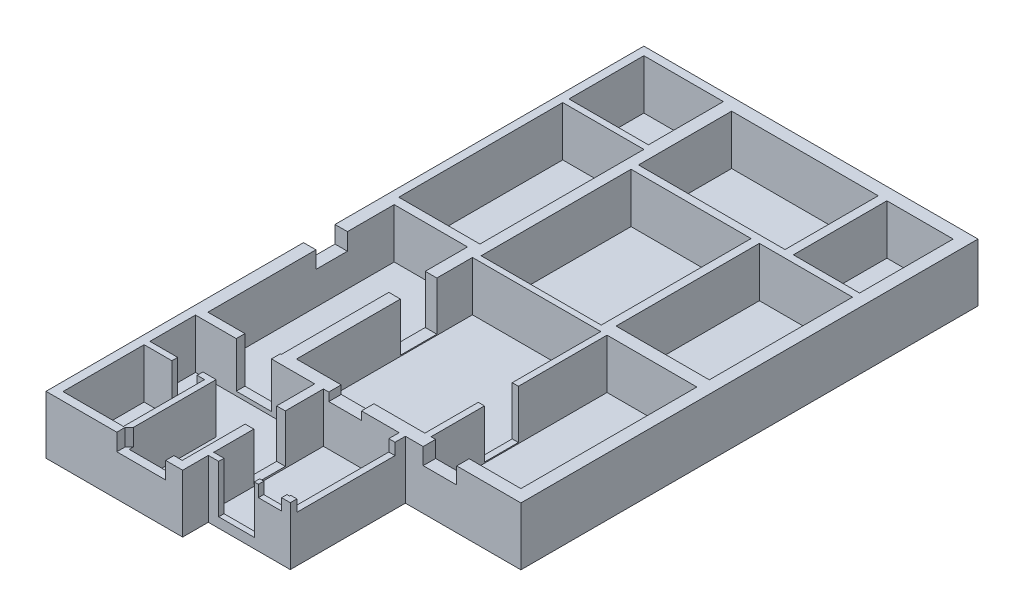
SolidWorks part; units mm, degrees
ref_plane "Спереди" through (0, 0, 0) normal (0, 0, 1) x (1, 0, 0)
ref_plane "Сверху" through (0, 0, 0) normal (0, 1, 0) x (1, 0, 0)
ref_plane "Справа" through (0, 0, 0) normal (1, 0, 0) x (0, 0, -1)
sketch "Эскиз1" plane through (0, 0, 0) normal (0, 1, 0) x (1, 0, 0)
  line L0 (-3589.779, 4492.6381) -> (-3589.779, 2682.6381)
  line L1 (-3789.779, -9747.3619) -> (-489.779, -9747.3619)
  line L2 (-3789.779, -9747.3619) -> (-3789.779, 4692.6381)
  line L3 (-3789.779, 4692.6381) -> (4280.221, 4692.6381)
  line L4 (4280.221, -6347.3619) -> (4280.221, 4692.6381)
  line L5 (-3789.779, -9747.3619) -> (4280.221, 4692.6381) construction
  line L6 (-3789.779, 4692.6381) -> (4280.221, -9747.3619) construction
  line L7 (-3589.779, 4492.6381) -> (-1669.779, 4492.6381)
  line L8 (-1629.779, 2532.6381) -> (-3589.779, 2532.6381)
  line L9 (3980.221, 4392.6381) -> (2380.221, 4392.6381)
  line L10 (-489.779, -9747.3619) -> (-489.779, -9127.3619)
  line L11 (-489.779, -9127.3619) -> (1490.221, -9127.3619)
  line L12 (1490.221, -9127.3619) -> (1490.221, -6347.3619)
  line L13 (1490.221, -6347.3619) -> (4280.221, -6347.3619)
  line L14 (4280.221, -6347.3619) -> (4280.221, -9747.3619) construction
  line L15 (-489.779, -9747.3619) -> (4280.221, -9747.3619) construction
  line L16 (3980.221, -6047.3619) -> (3980.221, -1797.3619)
  line L17 (1810.221, -6047.3619) -> (3980.221, -6047.3619)
  line L18 (3980.221, 4392.6381) -> (3980.221, 2132.6381)
  line L19 (3980.221, 2132.6381) -> (2380.221, 2132.6381)
  line L20 (2380.221, 2132.6381) -> (2380.221, 4392.6381)
  line L21 (2170.221, 4392.6381) -> (2170.221, 2142.6381)
  line L22 (2170.221, 4392.6381) -> (-1369.779, 4392.6381)
  line L23 (3980.221, -1797.3619) -> (1810.221, -1797.3619)
  line L24 (1810.221, -1797.3619) -> (1810.221, -6047.3619)
  line L25 (1730.221, -1497.3619) -> (3980.221, -1497.3619)
  line L26 (3980.221, -1497.3619) -> (3980.221, 1962.6381)
  line L27 (3980.221, 1962.6381) -> (1730.221, 1962.6381)
  line L28 (1730.221, 1962.6381) -> (1730.221, -1497.3619)
  line L29 (2170.221, 2142.6381) -> (-1369.779, 2142.6381)
  line L30 (-1369.779, 2142.6381) -> (-1369.779, 4392.6381)
  line L31 (-1669.779, 4492.6381) -> (-1669.779, 2682.6381)
  line L32 (-1669.779, 2682.6381) -> (-3589.779, 2682.6381)
  line L33 (-1629.779, 2532.6381) -> (-1629.779, -1427.3619)
  line L34 (-1629.779, -1427.3619) -> (-3589.779, -1427.3619)
  line L35 (1530.221, 1962.6381) -> (-1369.779, 1962.6381)
  line L36 (-1369.779, 1962.6381) -> (-1369.779, -1657.3619)
  line L37 (-1369.779, -1657.3619) -> (1530.221, -1657.3619)
  line L38 (1530.221, -1657.3619) -> (1530.221, 1962.6381)
  line L39 (-699.779, -6347.3619) -> (-699.779, -9547.3619)
  line L40 (-699.779, -9547.3619) -> (-1979.779, -9547.3619)
  line L41 (-3579.779, -9547.3619) -> (-3579.779, -7587.3619)
  line L42 (-3579.779, -6347.3619) -> (-699.779, -6347.3619)
  line L43 (1340.221, -8997.3619) -> (-489.779, -8997.3619)
  line L44 (-489.779, -8997.3619) -> (-489.779, -6347.3619)
  line L45 (-489.779, -6347.3619) -> (1340.221, -6347.3619)
  line L46 (1340.221, -6347.3619) -> (1340.221, -8997.3619)
  line L47 (-1439.779, -1797.3619) -> (-1439.779, -6047.3619)
  line L48 (-1439.779, -6047.3619) -> (1660.221, -6047.3619)
  line L49 (1660.221, -6047.3619) -> (1660.221, -1797.3619)
  line L50 (1660.221, -1797.3619) -> (-1439.779, -1797.3619)
  line L51 (-1719.779, -6137.3619) -> (-1719.779, -1637.3619)
  line L52 (-1719.779, -1637.3619) -> (-3489.779, -1637.3619)
  line L53 (-3489.779, -1637.3619) -> (-3489.779, -6137.3619)
  line L54 (-3489.779, -6137.3619) -> (-1719.779, -6137.3619)
  line L55 (-3579.779, -7447.3619) -> (-1979.779, -7447.3619)
  line L56 (-1979.779, -7447.3619) -> (-1979.779, -9547.3619)
  line L57 (-2119.779, -7587.3619) -> (-2119.779, -9547.3619)
  line L58 (-2119.779, -7587.3619) -> (-3579.779, -7587.3619)
  line L59 (-3579.779, -7447.3619) -> (-3579.779, -6347.3619)
  line L60 (-2119.779, -9547.3619) -> (-3579.779, -9547.3619)
  line L61 (-3589.779, 2532.6381) -> (-3589.779, -1427.3619)
  point P4 (245.221, -2527.3619)
  point P5 (-3789.779, 4492.6381)
  point P6 (-3789.779, 2682.6381)
  point P7 (-3789.779, 2532.6381)
  point P8 (-3789.779, -1427.3619)
  point P9 (-3589.779, 4692.6381)
  point P12 (-1669.779, 4692.6381)
  point P13 (3980.221, 4692.6381)
  point P15 (-1629.779, 2532.6381)
  point P16 (-1369.779, 4692.6381)
  point P17 (2170.221, 4692.6381)
  point P18 (2380.221, 4692.6381)
  point P19 (4280.221, 4392.6381)
  point P22 (-489.779, -9747.3619)
  point P23 (-489.779, -9127.3619)
  point P24 (1490.221, -9127.3619)
  point P25 (-3789.779, -6347.3619)
  point P26 (1490.221, -6347.3619)
  point P32 (4280.221, -6047.3619)
  point P33 (3980.221, -6347.3619)
  point P36 (1810.221, -6047.3619)
  point P38 (1810.221, -1797.3619)
  point P39 (4280.221, -1497.3619)
  point P40 (4280.221, 1962.6381)
  point P41 (4280.221, 2132.6381)
  point P42 (2380.221, 2132.6381)
  point P48 (1730.221, -1497.3619)
  point P59 (1530.221, 1962.6381)
  point P61 (1530.221, -1657.3619)
  point P64 (-3579.779, -9747.3619)
  point P67 (-699.779, -6347.3619)
  point P68 (-699.779, -9547.3619)
  point P71 (1340.221, -8997.3619)
  point P76 (1660.221, -6047.3619)
  point P79 (-1439.779, -1797.3619)
  point P83 (-1719.779, -6137.3619)
  point P85 (-3489.779, -6137.3619)
  point P86 (-1719.779, -1637.3619)
  point P90 (-1979.779, -7447.3619)
  point P92 (-1979.779, -7587.3619)
  point P93 (-2119.779, -7447.3619)
  dimension "D1" = 8070
  dimension "D2" = 14440
  dimension "D3" = 6120
  dimension "D4" = 200
  dimension "D5" = 1810
  dimension "D6" = 3960
  dimension "D7" = 200
  dimension "D8" = 2120
  dimension "D9" = 300
  dimension "D10" = 300
  dimension "D11" = 1600
  dimension "D12" = 3540
  dimension "D13" = 300
  dimension "D14" = 3300
  dimension "D15" = 620
  dimension "D16" = 1980
  dimension "D17" = 3400
  dimension "D18" = 300
  dimension "D19" = 300
  dimension "D20" = 4250
  dimension "D21" = 2170
  dimension "D22" = 300
  dimension "D23" = 3460
  dimension "D24" = 2260
  dimension "D25" = 2250
  dimension "D26" = 2250
  dimension "D27" = 1960
  dimension "D28" = 2900
  dimension "D29" = 3620
  dimension "D30" = 210
  dimension "D31" = 2880
  dimension "D32" = 3200
  dimension "D33" = 2650
  dimension "D34" = 1830
  dimension "D35" = 150
  dimension "D36" = 3100
  dimension "D37" = 4250
  dimension "D38" = 280
  dimension "D39" = 210
  dimension "D40" = 1770
  dimension "D41" = 4500
  dimension "D42" = 1600
  dimension "D43" = 2100
  dimension "D44" = 140
  dimension "D45" = 140
extrude "Стены" add sketch "Эскиз1" along normal blind 2580
sketch "Эскиз4" plane through (0, 0, 0) normal (0, 1, 0) x (1, 0, 0)
  line L0 (-3789.779, 4692.6381) -> (4280.221, 4692.6381)
  line L1 (4280.221, 4692.6381) -> (4280.221, -6347.3619)
  line L2 (4280.221, -6347.3619) -> (1490.221, -6347.3619)
  line L3 (1490.221, -6347.3619) -> (1490.221, -9127.3619)
  line L4 (1490.221, -9127.3619) -> (-489.779, -9127.3619)
  line L5 (-489.779, -9127.3619) -> (-489.779, -9747.3619)
  line L6 (-489.779, -9747.3619) -> (-3789.779, -9747.3619)
  line L7 (-3789.779, -9747.3619) -> (-3789.779, 4692.6381)
extrude "Пол" add sketch "Эскиз4" against normal blind 200
sketch "Эскиз5" plane through (-3489.779, 0, 0) normal (1, 0, 0) x (0, 0, -1)
  line L0 (-1637.3619, 2580) -> (-1637.3619, 0) construction
  line L2 (-1637.3619, 0) -> (-6137.3619, 0) construction
  line L3 (-2767.3619, 790) -> (-3527.3619, 790)
  line L4 (-2767.3619, 790) -> (-2767.3619, 2080)
  line L5 (-2767.3619, 2080) -> (-3527.3619, 2080)
  line L6 (-3527.3619, 790) -> (-3527.3619, 2080)
  line L7 (-2767.3619, 790) -> (-3527.3619, 2080) construction
  line L8 (-2767.3619, 2080) -> (-3527.3619, 790) construction
  point P0 (-2767.3619, 790)
  point P6 (-3527.3619, 2080)
  point P10 (-3147.3619, 1435)
  dimension "D1" = 1130
  dimension "D2" = 790
  dimension "D3" = 760
  dimension "D4" = 1290
extrude "Окно коридор" cut sketch "Эскиз5" against normal through all
sketch "Эскиз7" plane through (0, 0, 9547.3619) normal (0, 0, -1) x (-1, 0, 0)
  line L0 (699.779, 2580) -> (699.779, 0) construction
  line L1 (899.779, 2010) -> (2079.779, 2010)
  line L2 (899.779, 2010) -> (899.779, 790)
  line L3 (899.779, 790) -> (2079.779, 790)
  line L4 (2079.779, 2010) -> (2079.779, 790)
  line L5 (899.779, 2010) -> (2079.779, 790) construction
  line L6 (899.779, 790) -> (2079.779, 2010) construction
  line L7 (1979.779, 2580) -> (699.779, 2580) construction
  point P4 (1489.779, 1400)
  dimension "D1" = 200
  dimension "D2" = 1180
  dimension "D3" = 1220
  dimension "D4" = 570
extrude "Окно кухня" cut sketch "Эскиз7" against normal through all
chamfer "Фаска1" distance 100 angle 45 1 edges at (-1979.779, 1400, 9547.3619)
sketch "Эскиз10" plane through (0, 0, 6347.3619) normal (0, 0, 1) x (1, 0, 0)
  line L0 (-489.779, 2580) -> (-489.779, 0) construction
  line L1 (-359.779, 2070) -> (430.221, 2070)
  line L2 (-359.779, 2070) -> (-359.779, 1000)
  line L3 (-359.779, 1000) -> (430.221, 1000)
  line L4 (430.221, 2070) -> (430.221, 1000)
  line L5 (-359.779, 2070) -> (430.221, 1000) construction
  line L6 (-359.779, 1000) -> (430.221, 2070) construction
  line L7 (1340.221, 2580) -> (-489.779, 2580) construction
  point P4 (35.221, 1535)
  dimension "D1" = 130
  dimension "D2" = 790
  dimension "D3" = 1070
  dimension "D4" = 510
extrude "Окно зал" cut sketch "Эскиз10" against normal up to next
sketch "Эскиз11" plane through (0, 0, 8997.3619) normal (0, 0, -1) x (-1, 0, 0)
  line L0 (-1340.221, 2580) -> (-1340.221, 0) construction
  line L1 (-620.221, 1970) -> (239.779, 1970)
  line L2 (-620.221, 1970) -> (-620.221, 40)
  line L3 (-620.221, 40) -> (239.779, 40)
  line L4 (239.779, 1970) -> (239.779, 40)
  line L5 (-620.221, 1970) -> (239.779, 40) construction
  line L6 (-620.221, 40) -> (239.779, 1970) construction
  line L7 (489.779, 2580) -> (-1340.221, 2580) construction
  line L9 (489.779, 0) -> (-1340.221, 0) construction
  point P4 (-190.221, 1005)
  dimension "D1" = 720
  dimension "D2" = 860
  dimension "D3" = 610
  dimension "D4" = 40
extrude "Дверь входная" cut sketch "Эскиз11" against normal up to next
sketch "Эскиз12" plane through (0, 0, 7447.3619) normal (0, 0, -1) x (-1, 0, 0)
  line L0 (1979.779, 2580) -> (1979.779, 0) construction
  line L1 (2299.779, 1880) -> (2909.779, 1880)
  line L2 (2299.779, 1880) -> (2299.779, 150)
  line L3 (2299.779, 150) -> (2909.779, 150)
  line L4 (2909.779, 1880) -> (2909.779, 150)
  line L5 (2299.779, 1880) -> (2909.779, 150) construction
  line L6 (2299.779, 150) -> (2909.779, 1880) construction
  line L7 (3579.779, 2580) -> (1979.779, 2580) construction
  line L8 (3579.779, 0) -> (1979.779, 0) construction
  point P4 (2604.779, 1015)
  dimension "D1" = 320
  dimension "D2" = 610
  dimension "D3" = 700
  dimension "D4" = 150
extrude "Дверь ванная" cut sketch "Эскиз12" against normal up to next
sketch "Эскиз13" plane through (0, 0, 6137.3619) normal (0, 0, -1) x (-1, 0, 0)
  line L0 (1719.779, 2580) -> (1719.779, 0) construction
  line L1 (1744.779, 1950) -> (2594.779, 1950)
  line L2 (1744.779, 1950) -> (1744.779, 100)
  line L3 (1744.779, 100) -> (2594.779, 100)
  line L4 (2594.779, 1950) -> (2594.779, 100)
  line L5 (1744.779, 1950) -> (2594.779, 100) construction
  line L6 (1744.779, 100) -> (2594.779, 1950) construction
  line L7 (3489.779, 0) -> (1719.779, 0) construction
  line L8 (3489.779, 2580) -> (1719.779, 2580) construction
  point P4 (2169.779, 1025)
  dimension "D1" = 630
  dimension "D2" = 25
  dimension "D3" = 850
  dimension "D4" = 100
extrude "Дверь коридор" cut sketch "Эскиз13" against normal up to next
sketch "Эскиз15" plane through (-1719.779, 0, 0) normal (-1, 0, 0) x (0, 0, 1)
  line L0 (6137.3619, 2580) -> (6137.3619, 0) construction
  line L1 (2657.3619, 1800) -> (3537.3619, 1800)
  line L2 (2657.3619, 1800) -> (2657.3619, 25)
  line L3 (2657.3619, 25) -> (3537.3619, 25)
  line L4 (3537.3619, 1800) -> (3537.3619, 25)
  line L5 (2657.3619, 1800) -> (3537.3619, 25) construction
  line L6 (2657.3619, 25) -> (3537.3619, 1800) construction
  line L7 (6137.3619, 0) -> (1637.3619, 0) construction
  line L8 (6137.3619, 2580) -> (1637.3619, 2580) construction
  point P4 (3097.3619, 912.5)
  dimension "D1" = 2600
  dimension "D2" = 880
  dimension "D3" = 25
  dimension "D4" = 780
extrude "Дверь зал" cut sketch "Эскиз15" against normal up to next
sketch "Эскиз16" plane through (0, 0, 6047.3619) normal (0, 0, -1) x (-1, 0, 0)
  line L0 (-1810.221, 2580) -> (-1810.221, 0) construction
  line L1 (-2730.221, 2040) -> (-1920.221, 2040)
  line L2 (-2730.221, 2040) -> (-2730.221, 800)
  line L3 (-2730.221, 800) -> (-1920.221, 800)
  line L4 (-1920.221, 2040) -> (-1920.221, 800)
  line L5 (-2730.221, 2040) -> (-1920.221, 800) construction
  line L6 (-2730.221, 800) -> (-1920.221, 2040) construction
  line L7 (-1810.221, 2580) -> (-3980.221, 2580) construction
  point P4 (-2325.221, 1420)
  dimension "D1" = 110
  dimension "D2" = 810
  dimension "D3" = 1240
  dimension "D4" = 540
extrude "Окно спальня" cut sketch "Эскиз16" against normal up to next
sketch "Эскиз17" plane through (1660.221, 0, 0) normal (-1, 0, 0) x (0, 0, 1)
  line L0 (6047.3619, 2580) -> (6047.3619, 0) construction
  line L1 (3937.3619, 2080) -> (4757.3619, 2080)
  line L2 (3937.3619, 2080) -> (3937.3619, 25)
  line L3 (3937.3619, 25) -> (4757.3619, 25)
  line L4 (4757.3619, 2080) -> (4757.3619, 25)
  line L5 (3937.3619, 2080) -> (4757.3619, 25) construction
  line L6 (3937.3619, 25) -> (4757.3619, 2080) construction
  line L7 (6047.3619, 2580) -> (1797.3619, 2580) construction
  line L8 (6047.3619, 0) -> (1797.3619, 0) construction
  point P4 (4347.3619, 1052.5)
  dimension "D1" = 1290
  dimension "D2" = 820
  dimension "D3" = 500
  dimension "D4" = 25
extrude "Дверь спальня" cut sketch "Эскиз17" against normal up to next
sketch "Эскиз19" plane through (0, 0, 8997.3619) normal (0, 0, -1) x (-1, 0, 0)
  line L0 (-620.221, 1970) -> (-620.221, 40) construction
  line L1 (-1280.221, 2070) -> (-720.221, 2070)
  line L2 (-1280.221, 2070) -> (-1280.221, 920)
  line L3 (-1280.221, 920) -> (-720.221, 920)
  line L4 (-720.221, 2070) -> (-720.221, 920)
  line L5 (-1280.221, 2070) -> (-720.221, 920) construction
  line L6 (-1280.221, 920) -> (-720.221, 2070) construction
  line L7 (489.779, 2580) -> (-1340.221, 2580) construction
  point P4 (-1000.221, 1495)
  point P11 (-1396.7321, 2838.3101)
  point P12 (-1024.9452, 2536.2208)
  dimension "D1" = 100
  dimension "D2" = 560
  dimension "D3" = 1150
  dimension "D4" = 510
extrude "Окно прихожка малое" cut sketch "Эскиз19" against normal up to next
sketch "Эскиз20" plane through (1340.221, 0, 0) normal (-1, 0, 0) x (0, 0, 1)
  line L0 (8997.3619, 2580) -> (6347.3619, 2580) construction
  line L1 (6597.3619, 2070) -> (8967.3619, 2070)
  line L2 (6597.3619, 2070) -> (6597.3619, 920)
  line L3 (6597.3619, 920) -> (8967.3619, 920)
  line L4 (8967.3619, 2070) -> (8967.3619, 920)
  line L5 (6597.3619, 2070) -> (8967.3619, 920) construction
  line L6 (6597.3619, 920) -> (8967.3619, 2070) construction
  line L7 (8997.3619, 2580) -> (8997.3619, 0) construction
  line L8 (6347.3619, 2580) -> (6347.3619, 0) construction
  point P4 (7782.3619, 1495)
  dimension "D1" = 510
  dimension "D2" = 30
  dimension "D3" = 1150
  dimension "D4" = 250
extrude "Окно прихожка большое" cut sketch "Эскиз20" against normal up to next
sketch "Эскиз21" plane through (0, 2580, 0) normal (0, 1, 0) x (1, 0, 0)
  line L1 (-3789.779, 4692.6381) -> (4306.0723, 4692.6381)
  line L2 (-3789.779, 4692.6381) -> (-3789.779, -9795.0202)
  line L3 (-3789.779, -9795.0202) -> (4306.0723, -9795.0202)
  line L4 (4306.0723, 4692.6381) -> (4306.0723, -9795.0202)
  line L5 (-3789.779, 4692.6381) -> (4306.0723, -9795.0202) construction
  line L6 (-3789.779, -9795.0202) -> (4306.0723, 4692.6381) construction
  point P4 (258.1467, -2551.191)
sketch "Эскиз22" plane through (-699.779, 0, 0) normal (-1, 0, 0) x (0, 0, 1)
  line L0 (6347.3619, 2580) -> (6347.3619, 0) construction
  line L1 (7267.3619, 1930) -> (8027.3619, 1930)
  line L2 (7267.3619, 1930) -> (7267.3619, 40)
  line L3 (7267.3619, 40) -> (8027.3619, 40)
  line L4 (8027.3619, 1930) -> (8027.3619, 40)
  line L5 (7267.3619, 1930) -> (8027.3619, 40) construction
  line L6 (7267.3619, 40) -> (8027.3619, 1930) construction
  line L7 (9547.3619, 0) -> (6347.3619, 0) construction
  line L9 (9547.3619, 2580) -> (6347.3619, 2580) construction
  point P4 (7647.3619, 985)
  dimension "D1" = 920
  dimension "D2" = 760
  dimension "D3" = 40
  dimension "D4" = 650
extrude "Дверь прихожая" cut sketch "Эскиз22" against normal up to next
extrude "Срез" cut sketch "Эскиз21" against normal blind 1380
